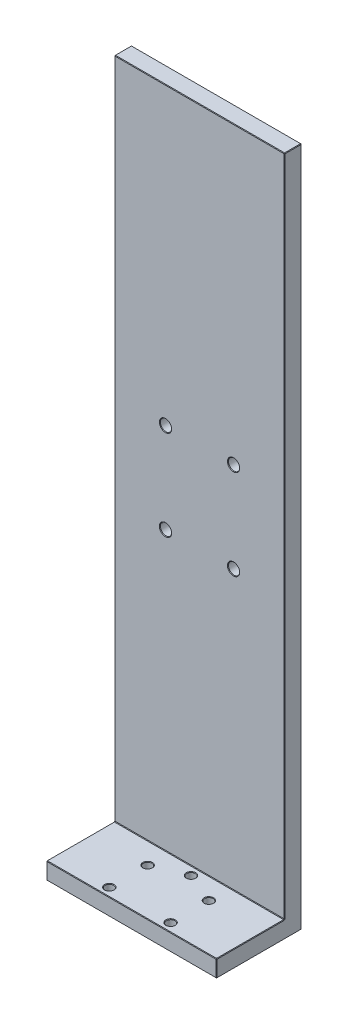
SolidWorks part; units mm, degrees
material "1060 Alloy"
ref_plane "Front Plane" through (0, 0, 0) normal (0, 0, 1) x (1, 0, 0)
ref_plane "Top Plane" through (0, 0, 0) normal (0, 1, 0) x (1, 0, 0)
ref_plane "Right Plane" through (0, 0, 0) normal (1, 0, 0) x (0, 0, -1)
sketch "Sketch1" plane through (0, 0, 0) normal (1, 0, 0) x (0, 0, -1)
  line L2 (0, 0) -> (0, 400)
  line L3 (0, 400) -> (-10, 400)
  line L4 (-10, 10) -> (-10, 400)
  line L5 (0, 0) -> (-50, 0)
  line L7 (-10, 10) -> (-50, 10)
  line L8 (-50, 0) -> (-50, 10)
  dimension "D1" = 10
  dimension "D2" = 400
  dimension "D3" = 50
extrude "Boss-Extrude1" add sketch "Sketch1" along normal mid plane 100
sketch "Sketch2" plane through (0, 0, 10) normal (0, 0, 1) x (1, 0, 0)
  line L0 (50, 0) -> (-50, 0) construction
  line L1 (20, 173.5) -> (-20, 173.5) construction
  line L2 (20, 173.5) -> (20, 226.5) construction
  line L3 (20, 226.5) -> (-20, 226.5) construction
  line L4 (-20, 173.5) -> (-20, 226.5) construction
  line L5 (20, 173.5) -> (-20, 226.5) construction
  line L6 (20, 226.5) -> (-20, 173.5) construction
  line L7 (50, 400) -> (50, 10) construction
  line L9 (-50, 400) -> (50, 400) construction
  line L10 (-50, 400) -> (-50, 0) construction
  line L11 (-50, 0) -> (50, 0) construction
  line L12 (50, 400) -> (50, 0) construction
  line L13 (-50, 400) -> (-50, 10) construction
  line L14 (-50, 200) -> (50, 200) construction
  circle A0 centre (-20, 226.5) radius 3.3
  circle A1 centre (20, 226.5) radius 3.3
  circle A2 centre (20, 173.5) radius 3.3
  circle A3 centre (-20, 173.5) radius 3.3
  point P0 (0, 200)
  dimension "D1" = 6.6
  dimension "D3" = 53
  dimension "D5" = 400
extrude "Cut-Extrude1" cut sketch "Sketch2" against normal blind 100
sketch "Sketch3" plane through (0, 10, 0) normal (0, 1, 0) x (1, 0, 0)
  line L0 (0, 0) -> (0, -33.75) construction
  line L1 (18, -22.5) -> (-18, -22.5) construction
  line L2 (18, -22.5) -> (18, -45) construction
  line L3 (18, -45) -> (-18, -45) construction
  line L4 (-18, -22.5) -> (-18, -45) construction
  line L5 (18, -22.5) -> (-18, -45) construction
  line L6 (18, -45) -> (-18, -22.5) construction
  line L9 (50, 0) -> (-50, 0) construction
  circle A0 centre (-18, -22.5) radius 2.5
  circle A1 centre (-18, -45) radius 2.5
  circle A2 centre (18, -45) radius 2.5
  circle A3 centre (18, -22.5) radius 2.5
  circle A4 centre (0, -15) radius 2.5
  point P0 (0, -33.75)
  dimension "D1" = 5
  dimension "D2" = 22.5
  dimension "D3" = 36
  dimension "D4" = 7.5
  dimension "D5" = 15
extrude "Cut-Extrude2" cut sketch "Sketch3" against normal blind 100
chamfer "Chamfer1" distance 0.3 angle 45 36 edges at (-18, 10, 25) (-18, 10, 47.5) (18, 10, 47.5) (18, 10, 25) (0, 10, 17.5) (-16.7, 226.5, 10) (23.3, 226.5, 10) (23.3, 173.5, 10) (-16.7, 173.5, 10) (50, 10, 30) (0, 10, 50) (-50, 10, 30) (0, 400, 10) (50, 205, 10) (0, 10, 10) (-50, 205, 10) (0, 0, 0) (0, 400, 0) (50, 5, 50) (50, 400, 5) (50, 200, 0) (50, 0, 25) (0, 0, 50) (-50, 5, 50) (-50, 400, 5) (-50, 200, 0) (-50, 0, 25) (-16.7, 226.5, 0) (23.3, 226.5, 0) (23.3, 173.5, 0) (-16.7, 173.5, 0) (-18, 0, 25) (-18, 0, 47.5) (18, 0, 47.5) (18, 0, 25) (0, 0, 17.5)
equation "\"M5_tap\"=4.2mm"
equation "\"M5_clearence\"=5.5mm"
equation "\"M6_tap\"=5mm"
equation "\"M6_clearence\"=6.6mm"
equation "\"D1@Sketch2\"=\"M6_clearence\""
equation "\"D1@Sketch3\"=\"M6_tap\""
equation "\"work_area_width\"=1100mm"
equation "\"work_area_depth\"=900mm"
equation "\"steel_base_width\"=80mm"
equation "\"steel_base_height\"=50mm"
equation "\"steel_base_wall_thickness\"=3mm"
equation "\"steel_base_radius\"=6mm"
equation "\"steel_sides_width\"=180mm"
equation "\"steel_sides_height\"=50mm"
equation "\"steel_sides_wall_thickness\"=5mm"
equation "\"steel_sides_radius\"=6mm"
equation "\"steel_gantry_width\"=120mm"
equation "\"steel_gantry_height\"=80mm"
equation "\"steel_gantry_wall_thickness\"=6mm"
equation "\"steel_gantry_radius\"=6mm"
equation "\"steel_rollers_width\"=80mm"
equation "\"steel_rollers_height\"=50mm"
equation "\"steel_rollers_wall_thickness\"=6mm"
equation "\"steel_rollers_radius\"=6mm"
equation "\"steel_zbox_width\"=400mm"
equation "\"steel_zbox_height\"=90mm"
equation "\"steel_zbox_wall_thickness\"=3mm"
equation "\"steel_zbox_radius\"=6mm"
equation "\"alu_zangle_width\"=400mm"
equation "\"alu_zangle_height\"=50mm"
equation "\"alu_zangle_wall_thickness\"=10mm"
equation "\"D1@Sketch1\"=\"alu_zangle_wall_thickness\""
equation "\"D2@Sketch1\"=\"alu_zangle_width\""
equation "\"D3@Sketch1\"=\"alu_zangle_height\""
equation "\"D5@Sketch2\"=\"steel_zbox_width\""
equation "\"D5@Sketch3\"=\"alu_zangle_wall_thickness\"+5"
